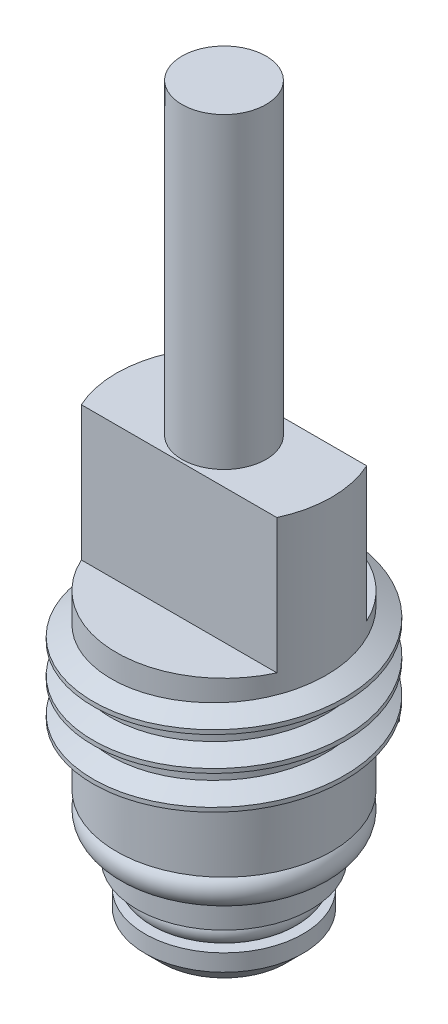
SolidWorks part; units mm, degrees
material "Brass"
ref_plane "Front Plane" through (0, 0, 0) normal (0, 0, 1) x (1, 0, 0)
ref_plane "Top Plane" through (0, 0, 0) normal (0, 1, 0) x (1, 0, 0)
ref_plane "Right Plane" through (0, 0, 0) normal (1, 0, 0) x (0, 0, -1)
sketch "Sketch1" plane through (0, 0, 0) normal (0, 0, 1) x (1, 0, 0)
  line L0 (0, -6751.5455) -> (0, 330825.7272) construction
  line L1 (1.875, -6.7373) -> (-1.875, -6.7373) construction
  line L2 (1.25, 13.7063) -> (-1.25, 13.7063)
  line L3 (1.25, 13.7063) -> (1.25, 4.5623)
  line L4 (1.25, 4.5623) -> (-1.25, 4.5623)
  line L5 (-1.25, 13.7063) -> (-1.25, 4.5623)
  line L6 (1.25, 13.7063) -> (-1.25, 4.5623) construction
  line L7 (1.25, 4.5623) -> (-1.25, 13.7063) construction
  line L8 (2.35, -7.1123) -> (-2.35, -7.1123)
  line L9 (2.35, -7.1123) -> (2.35, -8.1123)
  line L10 (2.35, -8.1123) -> (-2.35, -8.1123)
  line L11 (-2.35, -7.1123) -> (-2.35, -8.1123)
  line L12 (2.35, -7.1123) -> (-2.35, -8.1123) construction
  line L13 (2.35, -8.1123) -> (-2.35, -7.1123) construction
  line L14 (2.585, -5.5623) -> (-2.585, -5.5623)
  line L15 (2.585, -5.5623) -> (2.585, -6.3623)
  line L16 (2.585, -6.3623) -> (-2.585, -6.3623)
  line L17 (-2.585, -5.5623) -> (-2.585, -6.3623)
  line L18 (2.585, -5.5623) -> (-2.585, -6.3623) construction
  line L19 (2.585, -6.3623) -> (-2.585, -5.5623) construction
  line L20 (2.225, -4.5623) -> (-2.225, -4.5623)
  line L21 (2.225, -4.5623) -> (2.225, -5.5623)
  line L22 (2.225, -5.5623) -> (-2.225, -5.5623)
  line L23 (-2.225, -4.5623) -> (-2.225, -5.5623)
  line L24 (2.225, -4.5623) -> (-2.225, -5.5623) construction
  line L25 (2.225, -5.5623) -> (-2.225, -4.5623) construction
  line L26 (3.2, 4.5623) -> (-3.2, 4.5623)
  line L27 (3.2, 4.5623) -> (3.2, -4.5623)
  line L28 (3.2, -4.5623) -> (-3.2, -4.5623)
  line L29 (-3.2, 4.5623) -> (-3.2, -4.5623)
  line L30 (3.2, 4.5623) -> (-3.2, -4.5623) construction
  line L31 (3.2, -4.5623) -> (-3.2, 4.5623) construction
  line L32 (0, 13.7063) -> (0, -8.1123)
  circle A0 centre (-1.875, -6.7373) radius 0.375
  circle A1 centre (1.875, -6.7373) radius 0.375
  circle A2 centre (-2.7125, -5.0498) radius 0.4875
  circle A3 centre (2.7125, -5.0498) radius 0.4875
  point P1 (0, 9.1343)
  point P8 (0, -5.9623)
  point P9 (0, -7.6123)
  point P18 (0, -5.0623)
  point P23 (0, 0)
  point P35 (0, -6.7373)
  dimension "D12" = 4.5
  dimension "D2" = 6.4
  dimension "D3" = 4.7
  dimension "D4" = 1
  dimension "D5" = 0.75
  dimension "D6" = 5.17
  dimension "D7" = 0.8
  dimension "D8" = 4.45
  dimension "D9" = 1
  dimension "D10" = 2.5
  dimension "D11" = 9.144
  dimension "D13" = 21.8186
revolve "Revolve2" add sketch "Sketch1" angle 360 about L32 region at (-0.625, 9.1343, 0) region at (-1.6, 0, 0) region at (-1.1125, -5.0623, 0) region at (-1.2925, -5.9623, 0) region at (-1.175, -7.6123, 0)
revolve "Revolve3" add sketch "Sketch1<5>" angle 360 about L32 region at (-2.7125, -5.0498, 0) region at (-1.875, -6.7373, 0)
sketch "Sketch1<5>" plane through (0, 0, 0) normal (0, 0, 1) x (1, 0, 0) same geometry as "Sketch1"
sketch "Sketch2" plane through (0, 4.5623, 0) normal (0, 1, 0) x (1, 0, 0)
  line L0 (0, 3.2) -> (0, -3.2) construction
  line L1 (0, 1.335) -> (0, -1.335) construction
  line L2 (3.2, 3.2) -> (-3.2, 3.2)
  line L3 (3.2, 3.2) -> (3.2, 1.335)
  line L4 (3.2, 1.335) -> (-3.2, 1.335)
  line L5 (-3.2, 3.2) -> (-3.2, 1.335)
  line L6 (3.2, 3.2) -> (-3.2, 1.335) construction
  line L7 (3.2, 1.335) -> (-3.2, 3.2) construction
  line L8 (3.2, -1.335) -> (-3.2, -1.335)
  line L9 (3.2, -1.335) -> (3.2, -3.2)
  line L10 (3.2, -3.2) -> (-3.2, -3.2)
  line L11 (-3.2, -1.335) -> (-3.2, -3.2)
  line L12 (3.2, -1.335) -> (-3.2, -3.2) construction
  line L13 (3.2, -3.2) -> (-3.2, -1.335) construction
  circle A0 centre (0, 0) radius 3.2 construction
  point P5 (0, 2.2675)
  point P10 (0, -2.2675)
  point P18 (0, 0)
  dimension "D1" = 2.67
extrude "Cut-Extrude1" cut sketch "Sketch2" against normal blind 4
thread "Thread1" pitch 1 method extrude profile "Thread Profile1" start angle 0, offset 0, length 3.35, pitch 1, diameter 6.4
ref_plane "Plane1" through (-3.2, 0.5623, 0) normal (0, 0, 1) x (-1, 0, 0)
sketch "Thread Profile1" plane through (-3.2, 0.5623, 0) normal (0, 0, 1) x (-1, 0, 0)
  line L0 (0, 0) -> (0, 1) construction
  line L1 (0, 0) -> (0.5413, 0.3125)
  line L2 (0.5413, 0.3125) -> (0.5413, 0.4375)
  line L3 (0.5413, 0.4375) -> (0, 0.75)
  line L4 (0.5413, 0.375) -> (0, 0.375) construction
  line L11 (0, 0) -> (0, 0.75)
  point P2 (0, 0)
  dimension "Pitch" = 1
  dimension "Profile_Angle" = 60
  dimension "Profile_Land" = 0.125
  dimension "Profile_Height" = 0.5413
chamfer "Chamfer1" distance 0.5 1 edges at (-2.35, -8.1123, 0)
ref_plane "max_compression" through (0, 9.7623, 0) normal (0, 1, 0) x (1, 0, 0)
